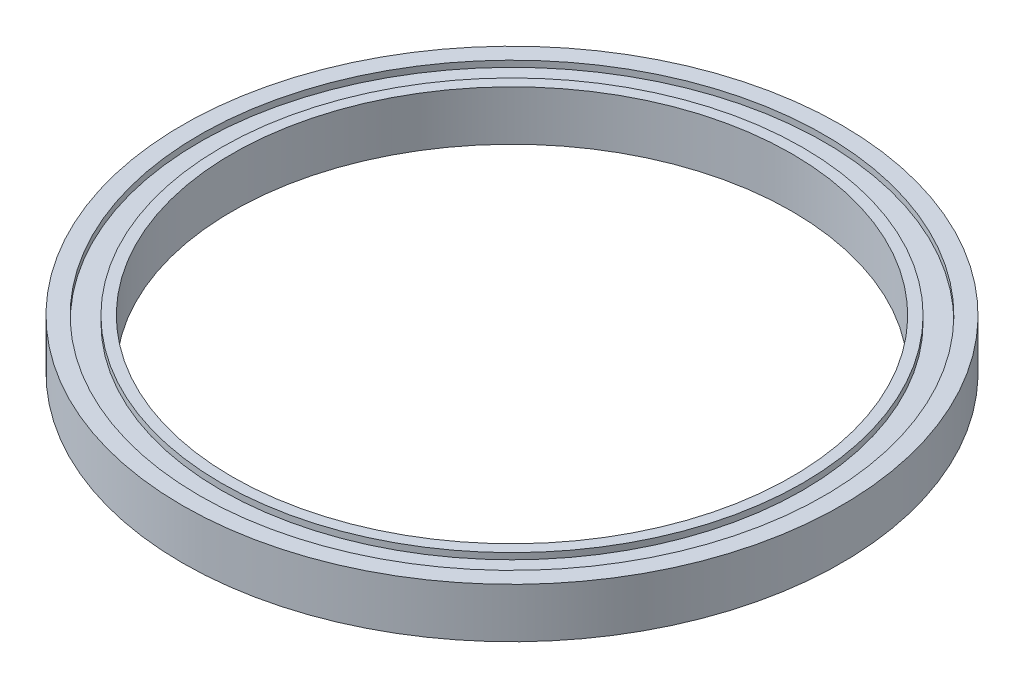
SolidWorks part; units mm, degrees
material "AISI 304"
ref_plane "前视基准面" through (0, 0, 0) normal (0, 0, 1) x (1, 0, 0)
ref_plane "上视基准面" through (0, 0, 0) normal (0, 1, 0) x (1, 0, 0)
ref_plane "右视基准面" through (0, 0, 0) normal (1, 0, 0) x (0, 0, -1)
sketch "草图1" plane through (0, 0, 0) normal (0, 1, 0) x (1, 0, 0)
  circle A0 centre (0, 0) radius 45
  circle A1 centre (0, 0) radius 53
  dimension "D1" = 90
  dimension "D2" = 106
extrude "凸台-拉伸1" add sketch "草图1" along normal blind 8
sketch "草图2" plane through (0, 8, 0) normal (0, 1, 0) x (1, 0, 0)
  circle A0 centre (0, 0) radius 46.75
  circle A1 centre (0, 0) radius 50.25
  dimension "D1" = 93.5
  dimension "D2" = 100.5
extrude "切除-拉伸1" cut sketch "草图2" against normal blind 1
extrude "切除-拉伸2" cut sketch "草图2<2>" along normal blind 1 from surface starting at face at (0, 0, 53)
sketch "草图2<2>" plane through (0, 8, 0) normal (0, 1, 0) x (1, 0, 0) same geometry as "草图2"
